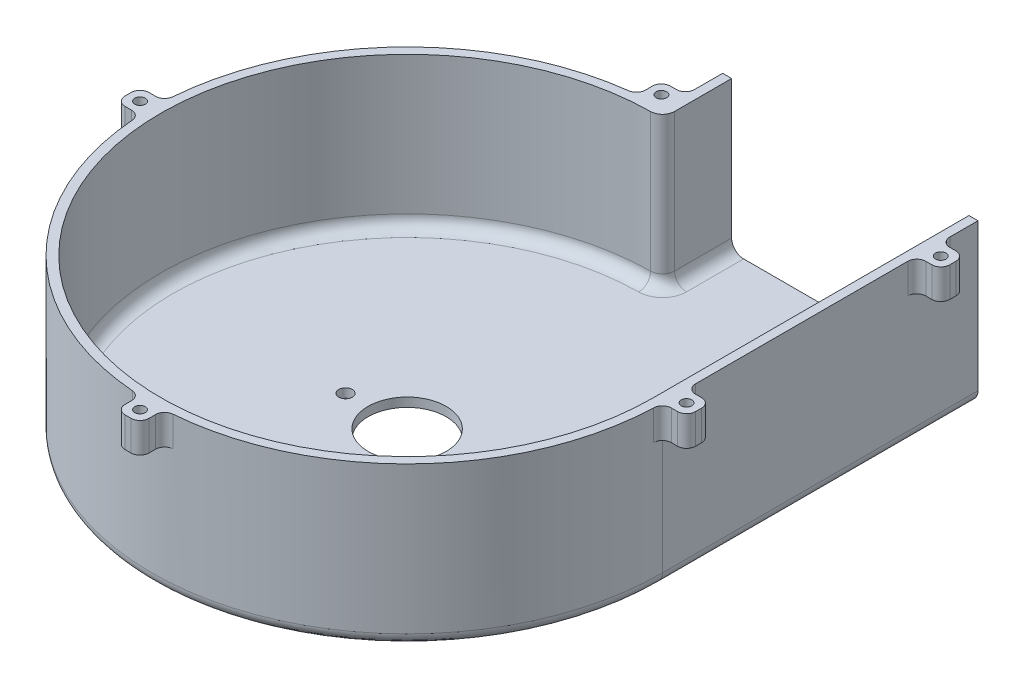
SolidWorks part; units mm, degrees
ref_plane "Front Plane" through (0, 0, 0) normal (0, 0, 1) x (1, 0, 0)
ref_plane "Top Plane" through (0, 0, 0) normal (0, 1, 0) x (1, 0, 0)
ref_plane "Right Plane" through (0, 0, 0) normal (1, 0, 0) x (0, 0, -1)
sketch "Sketch2" plane through (0, 0, 0) normal (0, 1, 0) x (1, 0, 0)
  line L0 (0, 85) -> (85, 85) construction
  line L2 (85, 0) -> (85, 105)
  line L3 (85, 105) -> (0, 105)
  line L4 (0, 85) -> (0, 105)
  circle A0 centre (0, 0) radius 59 construction
  arc A1 (0, 85) -> (85, 0) centre (0, 0) ccw
  circle A2 centre (0, 0) radius 20.5 construction
  circle A3 centre (20.5, 0) radius 2.25
  circle A4 centre (-20.5, 0) radius 2.25
  circle A5 centre (0, 0) radius 13
  dimension "D1" = 118
  dimension "D2" = 85
  dimension "D4" = 4.5
  dimension "D6" = 26
  dimension "D5" = 41
  dimension "D7" = 20
extrude "Boss-Extrude1" add sketch "Sketch2" along normal blind 3
sketch "Sketch3" plane through (0, 3, 0) normal (0, 1, 0) x (1, 0, 0)
  line L3 (85, 105) -> (0, 105) construction
  line L4 (0, 105) -> (3, 105)
  line L5 (82, 105) -> (85, 105)
  line L6 (82, 0) -> (82, 102)
  line L7 (82, 102) -> (3, 102)
  line L8 (3, 102) -> (3, 81.9451)
  line L9 (82, 0) -> (82, 105)
  line L11 (3, 105) -> (3, 81.9451)
  line L12 (85, 0) -> (85, 105)
  line L13 (85, 105) -> (0, 105)
  line L14 (0, 105) -> (0, 85)
  line L15 (85, 0) -> (85, 105)
  line L17 (0, 105) -> (0, 85)
  arc A2 (3, 81.9451) -> (82, 0) centre (0, 0) ccw
  arc A3 (3, 81.9451) -> (82, 0) centre (0, 0) ccw
  arc A4 (0, 85) -> (85, 0) centre (0, 0) ccw
  arc A5 (0, 85) -> (85, 0) centre (0, 0) ccw
  dimension "D1" = 3
  dimension "D2" = 0
extrude "Boss-Extrude2" add sketch "Sketch3" along normal blind 50
sketch "Sketch4" plane through (0, 53, 0) normal (0, 1, 0) x (1, 0, 0)
  line L0 (-4, 92.6227) -> (-4, 84.6227) construction
  line L1 (0, 92.6227) -> (-8, 92.6227)
  line L2 (0, 92.6227) -> (0, 85)
  line L4 (-8, 92.6227) -> (-8, 84.6227)
  line L5 (85, 92.6227) -> (93, 92.6227)
  line L6 (85, 92.6227) -> (85, 84.6227)
  line L7 (85, 84.6227) -> (93, 84.6227)
  line L8 (93, 92.6227) -> (93, 84.6227)
  line L9 (89, 92.6227) -> (89, 84.6227) construction
  line L10 (0, 85) -> (0, 84.6227) construction
  line L11 (0, 84.6227) -> (-8, 84.6227) construction
  line L13 (85, 0) -> (85, 105) construction
  line L14 (-92.9058, 0) -> (-84.9058, 0) construction
  line L15 (-84.9058, 4) -> (-92.9058, 4)
  line L16 (-84.9058, 4) -> (-84.9058, -4)
  line L17 (-84.9058, -4) -> (-92.9058, -4)
  line L18 (-92.9058, 4) -> (-92.9058, -4)
  line L19 (0, -84.9058) -> (0, -92.9058) construction
  line L20 (-4, -84.9058) -> (4, -84.9058)
  line L21 (-4, -84.9058) -> (-4, -92.9058)
  line L22 (-4, -92.9058) -> (4, -92.9058)
  line L23 (4, -84.9058) -> (4, -92.9058)
  line L24 (93, 4) -> (85, 4) construction
  line L25 (85, 0) -> (93, 0)
  line L26 (85, 0) -> (85, 8)
  line L27 (85, 8) -> (93, 8)
  line L28 (93, 0) -> (93, 8)
  circle A0 centre (-4, 88.6227) radius 1.75
  circle A1 centre (89, 88.6227) radius 1.75
  arc A2 (0, 85) -> (85, 0) centre (0, 0) ccw construction
  circle A3 centre (-88.9058, 0) radius 1.75
  circle A4 centre (0, -88.9058) radius 1.75
  circle A5 centre (89, 4) radius 1.75
  arc M8 (0, 85) -> (85, 0) centre (0, 0) ccw
  line M9 (85, 0) -> (85, 105)
  line M15 (0, 105) -> (0, 85)
  dimension "D5" = 3.5
  dimension "D6" = 3.5
  dimension "D8" = 3.5
  dimension "D10" = 3.5
  dimension "D12" = 3.5
  dimension "D1" = 8
  dimension "D2" = 8
  dimension "D3" = 8
  dimension "D4" = 8
  dimension "D7" = 8
  dimension "D9" = 8
  dimension "D11" = 8
extrude "Boss-Extrude3" add sketch "Sketch4" against normal blind 10 contours L23 L21 L22 A4 M8 | L15 L18 L17 A3 M8 | L25 L28 L27 A5 M9 | L8 L5 L7 A1 M9 | L1 L4 A0 M8 M15 region at (-0.1131, 53, -88.8113) region at (85.1131, 53, -88.6227) region at (85.1131, 53, -4) region at (0, 53, 85.1131) region at (-85.1131, 53, 0)
fillet "Fillet1" radius 3 19 edges at (85, 48, -92.6227) (93, 48, -92.6227) (93, 48, -84.6227) (85, 48, -84.6227) (85, 48, -8) (93, 48, -8) (93, 48, 0) (85, 48, 0) (4, 48, 84.9058) (4, 48, 92.9058) (-4, 48, 92.9058) (-4, 48, 84.9058) (-84.9058, 48, 4) (-92.9058, 48, 4) (-92.9058, 48, -4) (-84.9058, 48, -4) (-8, 48, -84.6227) (0, 48, -92.6227) (-8, 48, -92.6227)
fillet "Fillet2" radius 4 1 edges at (3, 28, -81.9451)
fillet "Fillet3" radius 4 4 edges at (82, 3, -52.5) (3, 3, -95.4971) (1.8448, 3, -83.1823) (-57.6447, 3, 58.3189)
fillet "Fillet4" radius 4 4 edges at (-60.1041, 0, 60.1041) (85, 0, -52.5) (0, 21.5, -85) (0, 0, -95)
